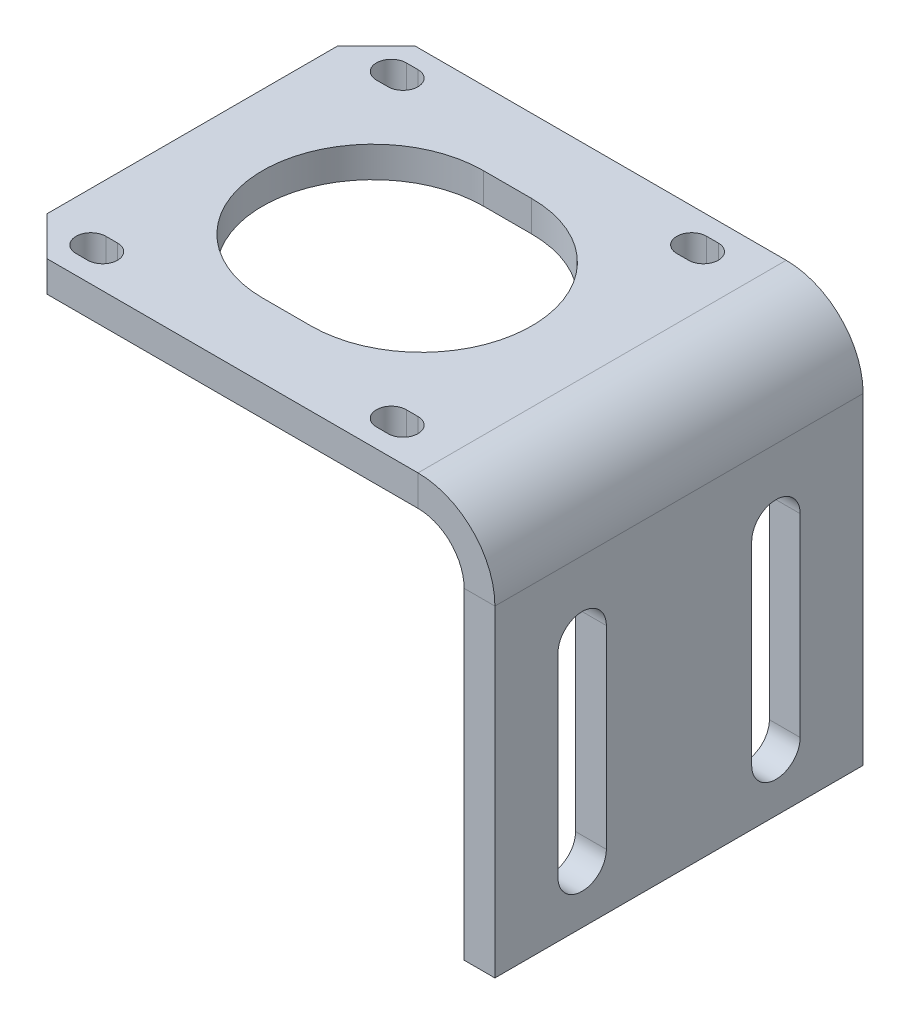
SolidWorks part; units mm, degrees
note: The reader was unsure of these and kept them because the rebuilt part matched: flange length of "Edge-Flange1".
ref_plane "Front Plane" through (0, 0, 0) normal (0, 0, 1) x (1, 0, 0)
ref_plane "Top Plane" through (0, 0, 0) normal (0, 1, 0) x (1, 0, 0)
ref_plane "Right Plane" through (0, 0, 0) normal (1, 0, 0) x (0, 0, -1)
sketch "Sketch1" plane through (22.559, 0, 0) normal (-1, 0, 0) x (0, 0, 1)
  line L0 (209.8097, 275.9118) -> (209.8097, 25.9118) construction
  line L1 (210.8097, 35.9118) -> (248.8097, 35.9118)
  line L2 (210.8097, 35.9118) -> (210.8097, 73.9118)
  line L3 (210.8097, 73.9118) -> (248.8097, 73.9118)
  line L4 (248.8097, 35.9118) -> (248.8097, 73.9118)
  line L5 (249.8097, 275.9118) -> (249.8097, 25.9118) construction
  line L6 (243.1097, 25.9118) -> (249.8097, 25.9118) construction
  line L7 (215.6597, 73.9118) -> (243.9597, 73.9118) construction
  dimension "D1" = 1
  dimension "D2" = 1
  dimension "D3" = 10
base flange "Base-Flange1" sketch "Sketch1" thickness 3.175 reverse thickness direction yes parameters "D1"=0.7366
edge flange "Edge-Flange1" sketch "Sketch8" flange angle 90 flange length 47.0625 flange position material outside bend radius 4.7625 thickness 3.175 relief rectangular parameters "D6"=10
sketch "Sketch8" plane through (19.384, 73.9118, 0) normal (0, 1, 0) x (0, 0, -1)
  line L0 (-248.8097, 0) -> (-210.8097, 0) construction
  line L1 (-248.8097, 0) -> (-210.8097, 0)
  line L2 (-248.8097, 0) -> (-248.8097, 47.0625)
  line L3 (-248.8097, 47.0625) -> (-210.8097, 47.0625)
  line L4 (-210.8097, 47.0625) -> (-210.8097, 0)
  line L5 (-243.9597, 47.0625) -> (-215.6597, 47.0625) construction
  line L6 (-229.8097, 23.4125) -> (-229.8097, 28.4125) construction
  line L7 (-241.1978, 23.4125) -> (-241.1978, 28.4125)
  line L8 (-218.4216, 23.4125) -> (-218.4216, 28.4125)
  line L9 (-214.3097, 9.8106) -> (-214.3097, 11.0144) construction
  line L10 (-215.8501, 9.8106) -> (-215.8501, 11.0144)
  line L11 (-212.7694, 9.8106) -> (-212.7694, 11.0144)
  line L12 (-214.3097, 40.8106) -> (-214.3097, 42.0144) construction
  line L13 (-215.8501, 40.8106) -> (-215.8501, 42.0144)
  line L14 (-212.7694, 40.8106) -> (-212.7694, 42.0144)
  line L15 (-245.3097, 9.8106) -> (-245.3097, 11.0144) construction
  line L16 (-246.8501, 9.8106) -> (-246.8501, 11.0144)
  line L17 (-243.7694, 9.8106) -> (-243.7694, 11.0144)
  line L18 (-245.3097, 40.8106) -> (-245.3097, 42.0144) construction
  line L19 (-246.8501, 40.8106) -> (-246.8501, 42.0144)
  line L20 (-243.7694, 40.8106) -> (-243.7694, 42.0144)
  circle A0 centre (-229.8097, 25.9125) radius 2.5 construction
  arc A1 (-241.1978, 23.4125) -> (-218.4216, 23.4125) centre (-229.8097, 23.4125) ccw
  arc A2 (-218.4216, 28.4125) -> (-241.1978, 28.4125) centre (-229.8097, 28.4125) ccw
  arc A4 (-215.8501, 9.8106) -> (-212.7694, 9.8106) centre (-214.3097, 9.8106) ccw
  arc A5 (-212.7694, 11.0144) -> (-215.8501, 11.0144) centre (-214.3097, 11.0144) ccw
  arc A6 (-215.8501, 40.8106) -> (-212.7694, 40.8106) centre (-214.3097, 40.8106) ccw
  arc A7 (-212.7694, 42.0144) -> (-215.8501, 42.0144) centre (-214.3097, 42.0144) ccw
  arc A8 (-246.8501, 9.8106) -> (-243.7694, 9.8106) centre (-245.3097, 9.8106) ccw
  arc A9 (-243.7694, 11.0144) -> (-246.8501, 11.0144) centre (-245.3097, 11.0144) ccw
  arc A10 (-246.8501, 40.8106) -> (-243.7694, 40.8106) centre (-245.3097, 40.8106) ccw
  arc A11 (-243.7694, 42.0144) -> (-246.8501, 42.0144) centre (-245.3097, 42.0144) ccw
  point P12 (-229.8097, 25.9125)
  point P21 (-214.3097, 10.4125)
  point P28 (-214.3097, 41.4125)
  point P36 (-245.3097, 10.4125)
  point P44 (-245.3097, 41.4125)
bend "EdgeBend1" bend radius 4.7625 bend angle 90 parameters "D5"=1
chamfer "Chamfer1" distance 4 angle 45 2 edges at (-27.6785, 75.4993, 210.8097) (-27.6785, 75.4993, 248.8097)
sketch "Sketch9" plane through (19.384, 0, 0) normal (-1, 0, 0) x (0, 0, 1)
  line L0 (239.8097, 61.6609) -> (239.8097, 41.6609) construction
  line L1 (242.3097, 61.6609) -> (242.3097, 41.6609)
  line L2 (237.3097, 61.6609) -> (237.3097, 41.6609)
  line L3 (219.8097, 61.6609) -> (219.8097, 41.6609) construction
  line L4 (222.3097, 61.6609) -> (222.3097, 41.6609)
  line L5 (217.3097, 61.6609) -> (217.3097, 41.6609)
  line L6 (219.8097, 51.6609) -> (239.8097, 51.6609) construction
  line L7 (239.8097, 41.6609) -> (239.8097, 25.9118) construction
  line L8 (239.8097, 25.9118) -> (219.8097, 25.9118) construction
  line L9 (219.8097, 25.9118) -> (219.8097, 41.6609) construction
  arc A0 (242.3097, 61.6609) -> (237.3097, 61.6609) centre (239.8097, 61.6609) ccw
  arc A1 (237.3097, 41.6609) -> (242.3097, 41.6609) centre (239.8097, 41.6609) ccw
  arc A2 (222.3097, 61.6609) -> (217.3097, 61.6609) centre (219.8097, 61.6609) ccw
  arc A3 (217.3097, 41.6609) -> (222.3097, 41.6609) centre (219.8097, 41.6609) ccw
  point P2 (239.8097, 51.6609)
  point P8 (219.8097, 51.6609)
  dimension "D2" = 5
  dimension "D1" = 20
extrude "Cut-Extrude1" cut sketch "Sketch9" against normal blind 10 normal cut yes
sketch "Bend-Lines1" plane through (0, 0, 0) normal (0, 1, 0) x (1, 0, 0)
sketch "Bounding-Box1" plane through (0, 0, 0) normal (0, 1, 0) x (1, 0, 0)
sheet metal parameters "Sheet-Metal(1)" thickness 3.175 parameters "D1"=0.7366
flat pattern "Flat-Pattern(1)" [suppressed]
sketch "Bend-Lines2" plane through (0, 0, 0) normal (0, 1, 0) x (1, 0, 0)
sketch "Bounding-Box2" [suppressed] plane through (0, 0, 0) normal (0, 1, 0) x (1, 0, 0)
sheet metal parameters "Sheet-Metal(2)" thickness 3.175 parameters "D1"=0.7366
flat pattern "Flat-Pattern(1)" [suppressed]
sketch "Bend-Lines2" plane through (0, 0, 0) normal (0, 1, 0) x (1, 0, 0)
sketch "Bounding-Box2" [suppressed] plane through (0, 0, 0) normal (0, 1, 0) x (1, 0, 0)
bend of the flat pattern "Flatten-<EdgeBend1>1"
sheet metal parameters "Sheet-Metal(3)" thickness 3.175 parameters "D1"=0.7366
flat pattern "Flat-Pattern(1)" [suppressed]
sketch "Bend-Lines2" plane through (0, 0, 0) normal (0, 1, 0) x (1, 0, 0)
sketch "Bounding-Box2" [suppressed] plane through (0, 0, 0) normal (0, 1, 0) x (1, 0, 0)
bend of the flat pattern "Flatten-<EdgeBend1>1"
